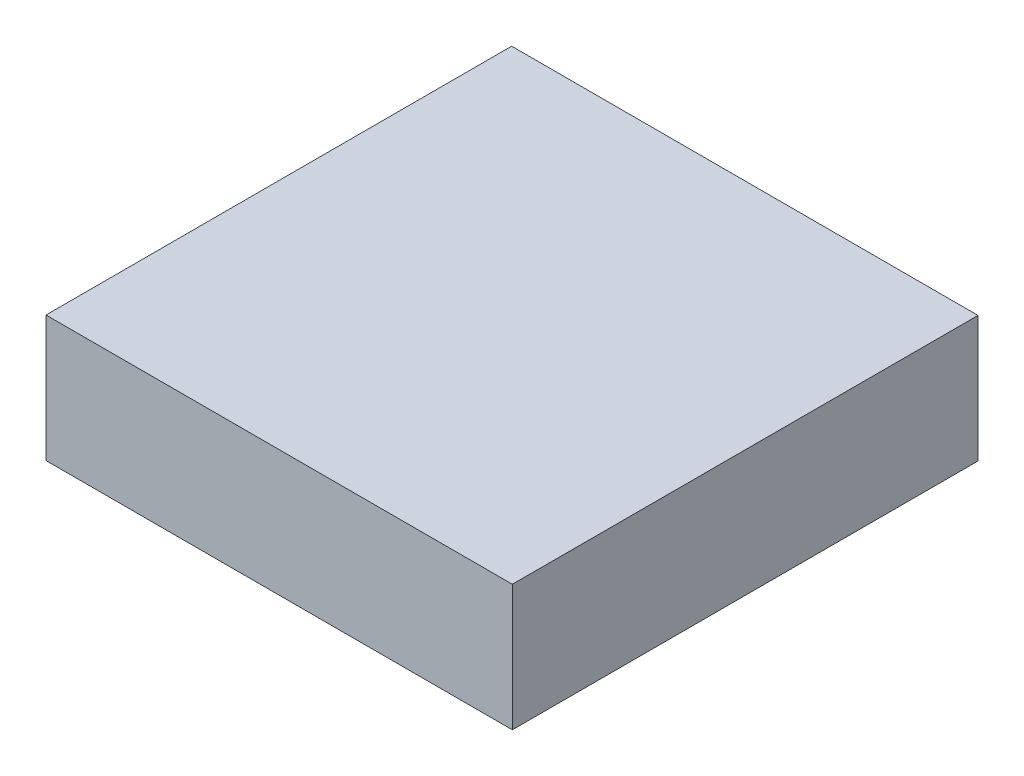
SolidWorks part; units mm, degrees
ref_plane "Front Plane" through (0, 0, 0) normal (0, 0, 1) x (1, 0, 0)
ref_plane "Top Plane" through (0, 0, 0) normal (0, 1, 0) x (1, 0, 0)
ref_plane "Right Plane" through (0, 0, 0) normal (1, 0, 0) x (0, 0, -1)
sketch "Sketch1" plane through (0, 0, 0) normal (0, 1, 0) x (1, 0, 0)
  circle A0 centre (0, 0) radius 11
  circle A1 centre (0, 30) radius 11
  circle A2 centre (24.5702, -12.3809) radius 11
  circle A3 centre (-24.4178, -12.4688) radius 11
  circle A4 centre (0, 30) radius 16
  circle A5 centre (-24.4178, -12.4688) radius 16
  circle A6 centre (24.5702, -12.3809) radius 16
  arc A7 (-14.8033, 23.9286) -> (-26.6184, 3.3791) centre (-28.6814, 18.2366) cw
  arc A8 (14.825, 23.9817) -> (26.7138, 3.4749) centre (28.7234, 18.3396) ccw
  arc A9 (-11.7582, -22.2531) -> (11.9457, -22.2106) centre (0.1103, -31.4259) cw
  point P12 (0.0508, 1.7168)
  dimension "D1" = 30
  dimension "D2" = 22
  dimension "D5" = 15
  dimension "D6" = 15
  dimension "D7" = 15
  dimension "D4" = 5
  dimension "D3" = 3
extrude "Boss-Extrude1" add sketch "Sketch1" along normal mid plane 7 contours A5 A9 A6 A8 A4 A7 A0 | A5 A3 | A6 A2 | A4 A1 region at (15.2593, 0, -27.0208) region at (0.03, 0, -13.2942) region at (-14.2081, 0, 0.7435) region at (36.2772, 0, 2.1501)
fillet "Fillet1" 2 edges at (-38.2599, 3.5, 20.4937) (-38.2599, -3.5, 20.4937) type full round first side face at (0, 3.5, 11) second side face at (0, -3.5, 11) middle face at (-28.7241, 0, 14.9653)
fillet "Fillet2" radius 0.5 6 edges at (-24.4178, -3.5, 23.4688) (-24.4178, 3.5, 23.4688) (24.5702, -3.5, 23.3809) (24.5702, 3.5, 23.3809) (0, -3.5, -19) (0, 3.5, -19)
fillet "Fillet3" radius 0.5 2 edges at (0, -3.5, 11) (0, 3.5, 11)
sketch "Croquis1" plane through (0, 3.5, 0) normal (0, 1, 0) x (1, 0, 0)
  line L1 (-50.8603, 50.783) -> (50.8603, 50.783)
  line L2 (-50.8603, 50.783) -> (-50.8603, -50.783)
  line L3 (-50.8603, -50.783) -> (50.8603, -50.783)
  line L4 (50.8603, 50.783) -> (50.8603, -50.783)
  line L5 (-50.8603, 50.783) -> (50.8603, -50.783) construction
  line L6 (-50.8603, -50.783) -> (50.8603, 50.783) construction
  point P0 (0, 0)
extrude "Saliente-Extruir1" add sketch "Croquis1" along normal blind 8 and the other way blind 2.5
sketch "Croquis2" plane through (0, 1, 0) normal (0, -1, 0) x (1, 0, 0)
  line L1 (-45.165, 46.018) -> (45.165, 46.018)
  line L2 (-45.165, 46.018) -> (-45.165, -46.018)
  line L3 (-45.165, -46.018) -> (45.165, -46.018)
  line L4 (45.165, 46.018) -> (45.165, -46.018)
  line L5 (-45.165, 46.018) -> (45.165, -46.018) construction
  line L6 (-45.165, -46.018) -> (45.165, 46.018) construction
  line L7 (-50.8603, 50.783) -> (50.8603, 50.783)
  line L8 (-50.8603, 50.783) -> (-50.8603, -50.783)
  line L9 (-50.8603, -50.783) -> (50.8603, -50.783)
  line L10 (50.8603, 50.783) -> (50.8603, -50.783)
  line L11 (-50.8603, 50.783) -> (50.8603, -50.783) construction
  line L12 (-50.8603, -50.783) -> (50.8603, 50.783) construction
  point P0 (0, 0)
  point P6 (0, 0)
extrude "Saliente-Extruir2" add sketch "Croquis2" along normal blind 17
